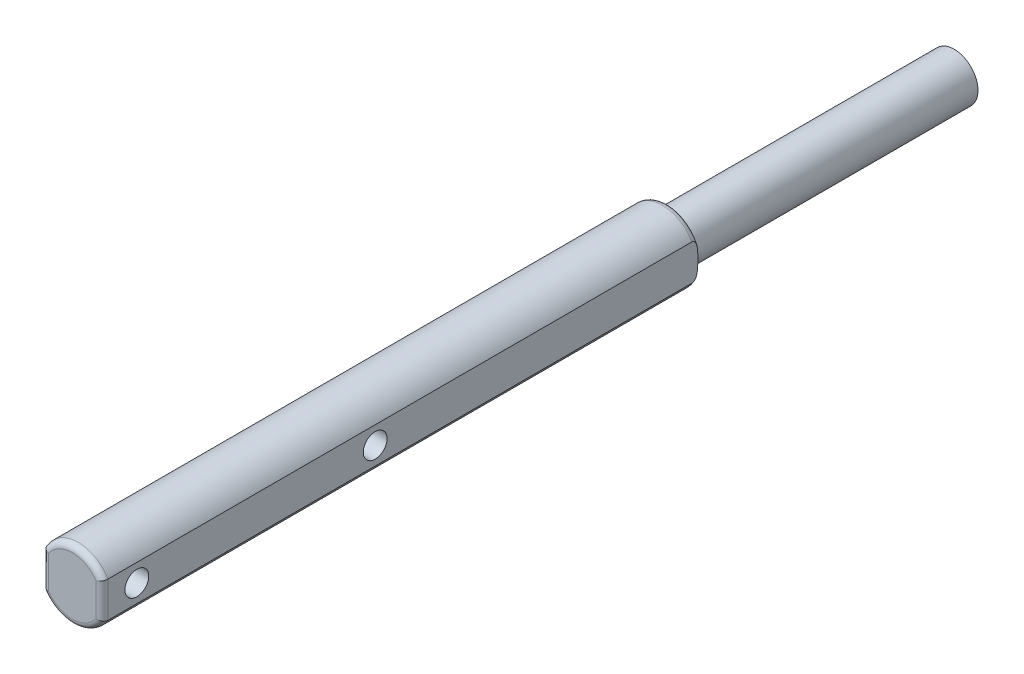
SolidWorks part; units mm, degrees
ref_plane "Plan de face" through (0, 0, 0) normal (0, 0, 1) x (1, 0, 0)
ref_plane "Plan de dessus" through (0, 0, 0) normal (0, 1, 0) x (1, 0, 0)
ref_plane "Plan de droite" through (0, 0, 0) normal (1, 0, 0) x (0, 0, -1)
sketch "Esquisse1" plane through (0, 0, 0) normal (0, 0, 1) x (1, 0, 0)
  line L0 (0, 0) -> (0, 25) construction
  line L1 (0, 25) -> (15, 25) construction
  line L2 (-25, 15) -> (-25, -15)
  line L3 (25, 15) -> (25, -15)
  circle A0 centre (0, 0) radius 29.1548
  circle A1 centre (0, 0) radius 20
  dimension "D3" = 40
  dimension "D1" = 15
  dimension "D2" = 25
  dimension "D4" = 30
extrude "Boss.-Extru.1" add sketch "Esquisse1" along normal blind 500 contours L3 A0 L2 A1 | A1 region at (0, 28.3866, 0) region at (0, 0, 0)
extrude "Boss.-Extru.2" add sketch "Esquisse1<4>" against normal blind 240 contours A1 region at (0, 0, 0)
sketch "Esquisse1<4>" plane through (0, 0, 0) normal (0, 0, 1) x (1, 0, 0) same geometry as "Esquisse1"
sketch "Esquisse2" plane through (-25, 0, 0) normal (-1, 0, 0) x (0, 0, 1)
  line L0 (500, 29.1548) -> (441.6905, -29.1548) construction
  line L2 (500, 15) -> (500, -15) construction
  line L3 (0, -29.1548) -> (500, -29.1548) construction
  line L4 (0, -29.1548) -> (500, -29.1548) construction
  circle A0 centre (470.8452, 0) radius 10
  circle A1 centre (270.8452, 0) radius 10
  point P11 (500, 29.1548)
  dimension "D2" = 20
  dimension "D3" = 20
  dimension "D4" = 200
  dimension "D1" = 45
extrude "Enlèv. mat.-Extru.1" cut sketch "Esquisse2" against normal through all
fillet "Congé1" radius 5 5 edges at (0, -29.1548, 500) (-25, 0, 500) (0, 29.1548, 500) (25, 0, 500) (0, 29.1548, 0)
